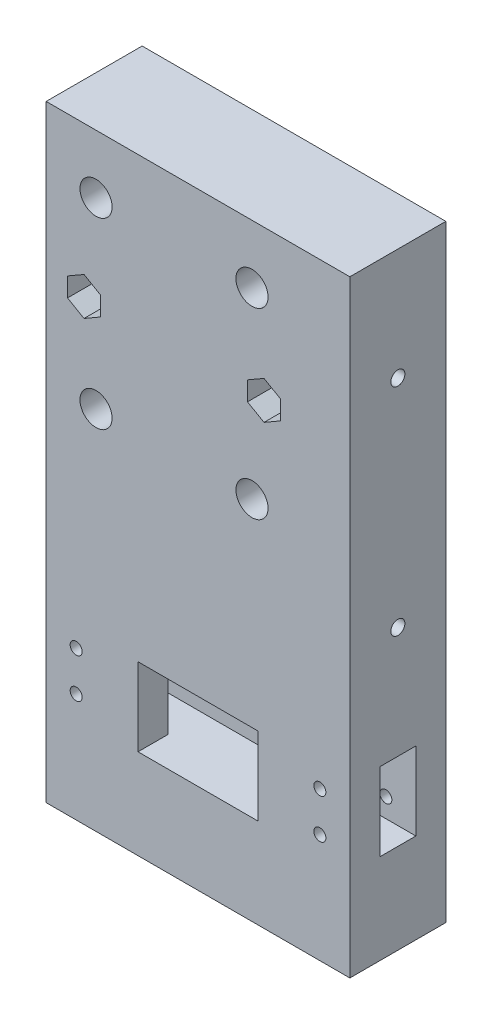
SolidWorks part; units mm, degrees
other "Markup1"
sketch "Sketch8" plane through (21.3115, 25, 0) normal (0.306, 0.1864, -0.9336) x (-0.9512, 0.0181, -0.3081)
ref_plane "Front Plane" through (0, 0, 0) normal (0, 0, 1) x (1, 0, 0)
ref_plane "Top Plane" through (0, 0, 0) normal (0, 1, 0) x (1, 0, 0)
ref_plane "Right Plane" through (0, 0, 0) normal (1, 0, 0) x (0, 0, -1)
sketch "Sketch1" plane through (0, 0, 0) normal (0, 0, 1) x (1, 0, 0)
  line L0 (0, 25) -> (0, -25) construction
  line L1 (21.3115, 25) -> (-21.3115, 25)
  line L2 (21.3115, 25) -> (21.3115, -25)
  line L3 (21.3115, -25) -> (-21.3115, -25)
  line L4 (-21.3115, 25) -> (-21.3115, -25)
  line L5 (21.3115, 25) -> (-21.3115, -25) construction
  line L6 (21.3115, -25) -> (-21.3115, 25) construction
  line L7 (-21.3115, 0) -> (21.3115, 0) construction
  circle A0 centre (-13, -15.25) radius 2.677
  circle A1 centre (13, -15.25) radius 2.677
  circle A2 centre (13, 15.25) radius 2.677
  circle A3 centre (-13, 15.25) radius 2.677
  point P0 (0, 0)
  dimension "D1" = 30.5
  dimension "D2" = 26
  dimension "D3" = 50
extrude "Boss-Extrude1" add sketch "Sketch1" along normal blind 16
sketch "Sketch2" plane through (0, 0, 0) normal (0, 0, 1) x (1, 0, 0)
  circle A0 centre (0, 0) radius 11.04
  dimension "D1" = 22.08
extrude "Cut-Extrude2" cut sketch "Sketch2" along normal blind 11
sketch "Sketch3" plane through (0, 0, 0) normal (0, 0, -1) x (-1, 0, 0)
  line L0 (0, 0) -> (-18.0234, 0) construction
  line L1 (0, 0) -> (0, 5.0894) construction
  circle A0 centre (-15, 0) radius 1.75
  circle A1 centre (15, 0) radius 1.75
  dimension "D1" = 15
  dimension "D2" = 3.5
extrude "Cut-Extrude3" cut sketch "Sketch3" against normal blind 10
sketch "Sketch9" plane through (0, 0, 0) normal (0, 0, -1) x (-1, 0, 0)
  line L0 (0, -11.04) -> (0, 11.04) construction
  line L1 (-15, 3.1754) -> (-17.75, 1.5877)
  line L2 (-17.75, 1.5877) -> (-17.75, -1.5877)
  line L3 (-17.75, -1.5877) -> (-15, -3.1754)
  line L4 (-15, -3.1754) -> (-12.25, -1.5877)
  line L5 (-12.25, -1.5877) -> (-12.25, 1.5877)
  line L6 (-12.25, 1.5877) -> (-15, 3.1754)
  line L7 (12.25, 1.5877) -> (15, 3.1754)
  line L8 (12.25, -1.5877) -> (12.25, 1.5877)
  line L9 (15, -3.1754) -> (12.25, -1.5877)
  line L10 (17.75, -1.5877) -> (15, -3.1754)
  line L11 (17.75, 1.5877) -> (17.75, -1.5877)
  line L12 (15, 3.1754) -> (17.75, 1.5877)
  circle A0 centre (-15, 0) radius 2.75 construction
  circle A1 centre (0, 0) radius 11.04 construction
  point P1 (-17.75, 0)
  dimension "D1" = 5.5
extrude "Cut-Extrude6" cut sketch "Sketch9" against normal through all from offset 5 offset against normal yes
sketch "Sketch30" plane through (0, -25, 0) normal (0, -1, 0) x (1, 0, 0)
  line L1 (-21.3115, 16) -> (21.3115, 16)
  line L2 (-21.3115, 16) -> (-21.3115, 0)
  line L3 (-21.3115, 0) -> (21.3115, 0)
  line L4 (21.3115, 16) -> (21.3115, 0)
extrude "Boss-Extrude8" add sketch "Sketch30" along normal blind 20.23
sketch "Sketch10" plane through (0, 0, 0) normal (0, 0, 1) x (1, 0, 0)
  line L0 (21.3115, -45.23) -> (-21.3115, -45.23)
  line L2 (-21.3115, -45.23) -> (-21.3115, -61.23)
  line L3 (-21.3115, -61.23) -> (21.3115, -61.23)
  line L4 (21.3115, -61.23) -> (21.3115, -45.23)
  dimension "D1" = 16
extrude "Boss-Extrude2" add sketch "Sketch10" along normal up to surface (16 mm away) up to face at (15, 0, 16)
sketch "Sketch14" plane through (-21.3115, 0, 0) normal (-1, 0, 0) x (0, 0, 1)
  line L0 (16, -61.23) -> (0, -61.23) construction
  line L1 (5, -61.23) -> (11, -61.23)
  line L2 (5, -61.23) -> (5, -48.23)
  line L3 (5, -48.23) -> (11, -48.23)
  line L4 (11, -61.23) -> (11, -48.23)
  line L7 (0, -61.23) -> (16, -61.23) construction
  point P6 (8, -61.23)
  point P7 (8, -61.23)
  dimension "D1" = 13
  dimension "D2" = 6
extrude "Cut-Extrude7" cut sketch "Sketch14" against normal through all
sketch "Sketch16" plane through (21.3115, 0, 0) normal (1, 0, 0) x (0, 0, -1)
  line L0 (-8, -48.23) -> (-8, 25)
  line L1 (-11, -48.23) -> (-5, -48.23) construction
  line L2 (-16, 25) -> (0, 25) construction
  line L4 (-16, 25) -> (0, 25)
  line L5 (-16, 25) -> (-16, -48.23)
  line L6 (-16, -48.23) -> (0, -48.23)
  line L7 (0, 25) -> (0, -48.23)
  line M6 (-11, -48.23) -> (-5, -48.23)
  line M9 (0, -61.23) -> (0, 25)
  line M10 (0, 25) -> (-16, 25)
  line M11 (-16, 25) -> (-16, -61.23)
extrude "Boss-Extrude3" add sketch "Sketch16" along normal blind 8 contours L6 L0 M11 M6 M10 | L6 L0 M6 M9 M10 region at (21.3115, -11.615, 12) region at (21.3115, -11.615, 4)
sketch "Sketch17" plane through (29.3115, 0, 0) normal (1, 0, 0) x (0, 0, -1)
  line L0 (-8, -48.23) -> (-8, 25)
  line L1 (-16, -48.23) -> (0, -48.23) construction
  line L2 (0, 25) -> (-16, 25) construction
  line L3 (-8, -11.615) -> (0, -11.615)
  line L4 (0, -48.23) -> (0, 25) construction
  circle A0 centre (-8, 6.385) radius 1.175
  circle A1 centre (-8, -29.615) radius 1.175
  point P8 (-8, -11.615)
  dimension "D2" = 2.35
  dimension "D1" = 18
extrude "Cut-Extrude9" cut sketch "Sketch17" against normal blind 8 contours L0 A0 | L0 A0 | A1 L0 | A1 L0 region at (29.3115, -29.615, 8.4987) region at (29.3115, 6.385, 8.4987) region at (29.3115, 6.385, 7.5013) region at (29.3115, -29.615, 7.5013)
sketch "Sketch18" plane through (0, 0, 0) normal (0, 0, -1) x (-1, 0, 0)
  line L0 (-25.3115, -48.23) -> (-25.3115, 25)
  line L1 (-29.3115, -48.23) -> (-21.3115, -48.23) construction
  line L2 (-29.3115, 25) -> (21.3115, 25) construction
  line L3 (-25.3115, -11.615) -> (-29.3115, -11.615)
  line L4 (-26.2115, 8.385) -> (-24.4115, 8.385)
  line L5 (-26.2115, 8.385) -> (-26.2115, 4.385)
  line L6 (-26.2115, 4.385) -> (-24.4115, 4.385)
  line L7 (-24.4115, 8.385) -> (-24.4115, 4.385)
  line L8 (-26.2115, 8.385) -> (-24.4115, 4.385) construction
  line L9 (-26.2115, 4.385) -> (-24.4115, 8.385) construction
  line L10 (-29.3115, -48.23) -> (-29.3115, 25) construction
  line L11 (-26.2115, -27.615) -> (-24.4115, -27.615)
  line L12 (-24.4115, -31.615) -> (-24.4115, -27.615)
  line L13 (-26.2115, -31.615) -> (-24.4115, -31.615)
  line L14 (-26.2115, -31.615) -> (-26.2115, -27.615)
  point P6 (-25.3115, 6.385)
  point P11 (-25.3115, -11.615)
  dimension "D1" = 18
  dimension "D2" = 4
  dimension "D3" = 1.8
extrude "Cut-Extrude10" cut sketch "Sketch18" against normal blind 10.2 contours L7 L4 L0 L6 | L5 L6 L0 L4 | L14 L11 L12 L13 region at (25.7615, 6.385, 0) region at (24.8615, 6.385, 0)
sketch "Sketch15" plane through (0, 0, 0) normal (0, 0, -1) x (-1, 0, 0)
  line L0 (21.3115, -61.23) -> (-21.3115, -61.23) construction
  line L1 (-29.3115, -23.2996) -> (21.3115, -23.2996)
  line L2 (-21.3115, -61.23) -> (-21.3115, -48.23)
  line L3 (-29.3115, -48.23) -> (-29.3115, 25) construction
  line L4 (-4, -23.2996) -> (-4, -61.23)
  line L7 (-21.3115, -61.23) -> (-21.3115, -48.23) construction
  line L8 (-21.3115, -48.23) -> (-21.3115, -61.23) construction
  line L9 (-21.3115, -54.73) -> (21.3115, -54.73)
  line L10 (21.3115, 25) -> (21.3115, -61.23) construction
  line L11 (21.3115, -54.73) -> (21.3115, -28)
  line L12 (21.3115, -28) -> (0, -28)
  line L13 (0, -28) -> (0, -61.23)
  circle A2 centre (16.3115, -58.03) radius 1
  circle A4 centre (16.3115, -51.43) radius 1
  point P11 (-21.3115, -61.23)
  dimension "D1" = 5
  dimension "D2" = 3.2
extrude "Cut-Extrude8" cut sketch "Sketch15" against normal through all and the other way through all contours A2 | A4
sketch "Sketch6" plane through (0, -48.23, 0) normal (0, -1, 0) x (1, 0, 0)
  line L0 (21.3115, 11) -> (-21.3115, 11) construction
  line L1 (4.517, 11) -> (-4.517, 11)
  line L2 (4.517, 11) -> (4.517, 14.85)
  line L3 (4.517, 14.85) -> (-4.517, 14.85)
  line L4 (-4.517, 11) -> (-4.517, 14.85)
  line L5 (4.517, 11) -> (-4.517, 14.85) construction
  line L6 (4.517, 14.85) -> (-4.517, 11) construction
  point P0 (0, 12.925)
  dimension "D1" = 3.85
extrude "Cut-Extrude5" cut sketch "Sketch6" against normal blind 50 and the other way through all
sketch "Sketch20" plane through (0, -48.23, 0) normal (0, -1, 0) x (-1, 0, 0)
  line L1 (-21.3115, -16) -> (-29.3115, -16)
  line L2 (-21.3115, -16) -> (-21.3115, 0)
  line L3 (-21.3115, 0) -> (-29.3115, 0)
  line L4 (-29.3115, -16) -> (-29.3115, 0)
extrude "Boss-Extrude5" add sketch "Sketch20" along normal up to surface (13 mm away) up to face at (0, -61.23, 13.2125)
sketch "Sketch21" plane through (0, -61.23, 0) normal (0, -1, 0) x (-1, 0, 0)
  line L0 (-29.3115, -16) -> (-29.3115, 0) construction
  line L1 (-21.3115, -11) -> (-29.3115, -11)
  line L2 (-21.3115, -11) -> (-21.3115, -5)
  line L3 (-21.3115, -5) -> (-29.3115, -5)
  line L4 (-29.3115, -11) -> (-29.3115, -5)
extrude "Cut-Extrude11" cut sketch "Sketch21" against normal up to surface (13 mm away) up to face at (0, -48.23, 9)
sketch "Sketch22" plane through (0, 0, 0) normal (0, 0, -1) x (-1, 0, 0)
  line L0 (21.3115, -61.23) -> (-29.3115, -61.23) construction
  line L1 (-29.3115, -61.23) -> (-29.3115, 25) construction
  circle A0 centre (-24.3115, -58.03) radius 1
  circle A3 centre (-24.3115, -51.43) radius 1
  dimension "D1" = 2
  dimension "D2" = 3.2
  dimension "D3" = 5
  dimension "D4" = 6.6
  dimension "D5" = 2
  dimension "D6" = 5
extrude "Cut-Extrude12" cut sketch "Sketch22" against normal through all
sketch "Sketch24" plane through (0, -61.23, 0) normal (0, -1, 0) x (1, 0, 0)
  line L1 (-21.3115, 5) -> (29.3115, 5)
  line L2 (-21.3115, 5) -> (-21.3115, 0)
  line L3 (-21.3115, 0) -> (29.3115, 0)
  line L4 (29.3115, 5) -> (29.3115, 0)
extrude "Boss-Extrude6" add sketch "Sketch24" along normal blind 15
sketch "Sketch25" plane through (0, 0, 5) normal (0, 0, 1) x (1, 0, 0)
  line L0 (29.3115, -76.23) -> (-21.3115, -76.23) construction
  line L1 (-21.3115, -76.23) -> (29.3115, -76.23)
  line L2 (-21.3115, -76.23) -> (-21.3115, -61.23)
  line L3 (-21.3115, -61.23) -> (29.3115, -61.23)
  line L4 (29.3115, -76.23) -> (29.3115, -61.23)
extrude "Boss-Extrude7" add sketch "Sketch25" along normal up to surface (11 mm away) up to face at (23.3115, -58.03, 16)
sketch "Sketch26" plane through (0, -76.23, 0) normal (0, -1, 0) x (1, 0, 0)
  line L0 (4, 16) -> (4, 0)
  line L1 (29.3115, 16) -> (-21.3115, 16) construction
  line L2 (-21.3115, 0) -> (29.3115, 0) construction
  line L3 (4, 8) -> (-21.3115, 8)
  line L4 (-21.3115, 16) -> (-21.3115, 0) construction
  circle A0 centre (-14, 8) radius 1
  circle A1 centre (22, 8) radius 1
  dimension "D1" = 2
  dimension "D2" = 18
extrude "Cut-Extrude13" cut sketch "Sketch26" against normal blind 10 contours L3 A0 | L3 A0 | A1 region at (-14, -76.23, 7.5756) region at (-14, -76.23, 8.4244) region at (22, -76.23, 8)
sketch "Sketch27" plane through (0, 0, 0) normal (0, 0, -1) x (-1, 0, 0)
  line L0 (-24.4115, -31.615) -> (-24.4115, -27.615) construction
  line L1 (-24.0015, -71.33) -> (-20.0015, -71.33)
  line L2 (-24.0015, -71.33) -> (-24.0015, -73.13)
  line L3 (-24.0015, -73.13) -> (-20.0015, -73.13)
  line L4 (-20.0015, -71.33) -> (-20.0015, -73.13)
  line L5 (-24.0015, -71.33) -> (-20.0015, -73.13) construction
  line L6 (-24.0015, -73.13) -> (-20.0015, -71.33) construction
  line L8 (-26.2115, -31.615) -> (-24.4115, -31.615) construction
  line L12 (-29.3115, -76.23) -> (-29.3115, 25) construction
  line L13 (21.3115, -76.23) -> (-29.3115, -76.23) construction
  line L14 (-29.3115, -49.5626) -> (21.3115, -49.5626)
  line L15 (21.3115, 25) -> (21.3115, -76.23) construction
  line L16 (-4, -49.5626) -> (-4, -76.23)
  line L17 (16.0015, -73.13) -> (12.0015, -73.13)
  line L18 (12.0015, -71.33) -> (12.0015, -73.13)
  line L19 (16.0015, -71.33) -> (12.0015, -71.33)
  line L20 (16.0015, -71.33) -> (16.0015, -73.13)
  point P0 (-22.0015, -72.23)
  dimension "D1" = 7.31
  dimension "D2" = 3.1
extrude "Cut-Extrude14" cut sketch "Sketch27" against normal blind 10.2 contours L4 L1 L2 L3 | L20 L19 L18 L17 region at (22.0015, -72.23, 0) region at (-14.0015, -72.23, 0)
sketch "Sketch29" plane through (0, 0, 16) normal (0, 0, 1) x (1, 0, 0)
  line L0 (-16.3115, -51.43) -> (24.3115, -58.03)
  line L1 (24.3115, -51.43) -> (-16.3115, -58.03)
  line L2 (-16.3115, -51.43) -> (24.3115, -51.43)
  line L3 (-16.3115, -51.43) -> (-16.3115, -58.03)
  line L4 (-16.3115, -58.03) -> (24.3115, -58.03)
  line L5 (24.3115, -51.43) -> (24.3115, -58.03)
  line L7 (-6, -48.23) -> (14, -48.23)
  line L8 (-6, -48.23) -> (-6, -61.23)
  line L9 (-6, -61.23) -> (14, -61.23)
  line L10 (14, -48.23) -> (14, -61.23)
  line L11 (-6, -48.23) -> (14, -61.23) construction
  line L12 (-6, -61.23) -> (14, -48.23) construction
  circle A0 centre (-16.3115, -51.43) radius 1 construction
  point P4 (4, -54.73)
  dimension "D1" = 13
  dimension "D2" = 20
extrude "Cut-Extrude15" cut sketch "Sketch29" against normal up to surface (5 mm away) contours L10 L7 L8 L2 | L10 L2 L8 L0 L1 | L0 L8 L1 | L10 L4 L8 L9 | L10 L0 L1 L8 L4 | L10 L1 L0 region at (4, -52.718, 16) region at (-2.6667, -54.73, 16) region at (4, -49.83, 16) region at (10.6667, -54.73, 16) region at (4, -56.742, 16) region at (4, -59.63, 16) up to face at (-16.3115, -59.03, 11)
